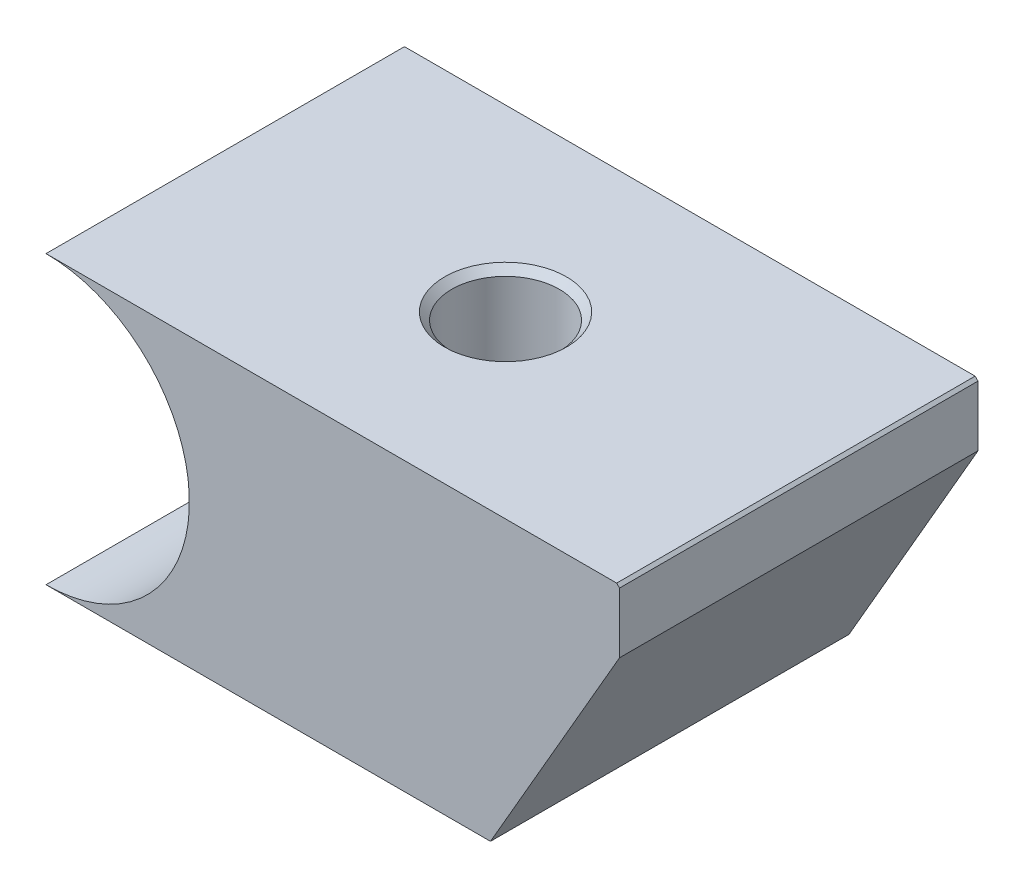
SolidWorks part; units mm, degrees
ref_plane "Front Plane" through (0, 0, 0) normal (0, 0, 1) x (1, 0, 0)
ref_plane "Top Plane" through (0, 0, 0) normal (0, 1, 0) x (1, 0, 0)
ref_plane "Right Plane" through (0, 0, 0) normal (1, 0, 0) x (0, 0, -1)
sketch "Sketch1" plane through (0, 0, 0) normal (0, 0, 1) x (1, 0, 0)
  line L1 (0, 0) -> (50.8, 0)
  line L3 (0, 25.4) -> (50.8, 25.4)
  line L4 (50.8, 0) -> (50.8, 25.4)
  arc A1 (0, 0) -> (0, 25.4) centre (0, 12.7) ccw
  dimension "D2" = 25.4
  dimension "D1" = 50.8
extrude "Boss-Extrude1" add sketch "Sketch1" along normal blind 31.75
chamfer "Chamfer1" distance 11.43 angle 60 1 edges at (50.8, 0, 15.875) first distance on face at (25.4, 0, 15.875)
hole_wizard "3/8 (0.375) Diameter Hole1" positions "Sketch4" profile "Sketch3" hole size "3/8" standard "ANSI Inch" end condition through all
sketch "Sketch4" plane through (0, 25.4, 0) normal (0, 1, 0) x (1, 0, 0)
  line L0 (50.8, -31.75) -> (50.8, 0) construction
  point P0 (24.8285, -15.875)
  point P5 (50.8, -15.875)
  dimension "D1" = 25.9715
sketch "Sketch3" plane through (24.8285, 25.4, 15.875) normal (1, 0, 0) x (0, 0, 1)
  line L0 (0, 0) -> (0, 25.4)
  line L1 (0, 25.4) -> (4.7625, 25.4)
  line L2 (4.7625, 25.4) -> (4.7625, 0.635)
  line L3 (4.7625, 0.635) -> (5.3975, 0)
  line L5 (5.3975, 0) -> (0, 0)
  line L6 (-4.7625, 0.635) -> (-5.3975, 0) construction
  line L11 (0, -6.35) -> (0, 107.95) construction
  dimension "Thru Hole Dia." = 9.525
  dimension "Thru Hole Depth" = 25.4
  dimension "Near C'Sink Dia." = 10.795
  dimension "Near C'Sink Angle" = 90
chamfer "Chamfer2" distance 0.254 angle 45 1 edges at (50.8, 25.4, 15.875)
